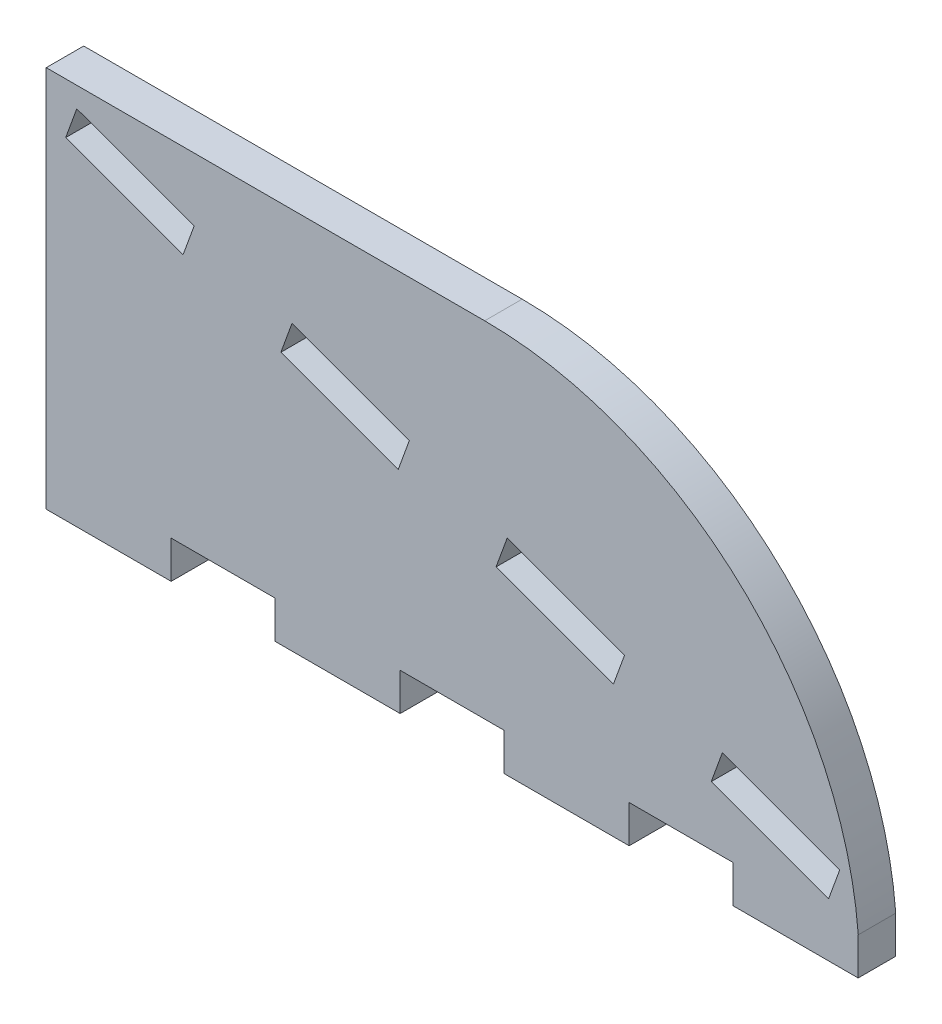
SolidWorks part; units mm, degrees
ref_plane "Front Plane" through (0, 0, 0) normal (0, 0, 1) x (1, 0, 0)
ref_plane "Top Plane" through (0, 0, 0) normal (0, 1, 0) x (1, 0, 0)
ref_plane "Right Plane" through (0, 0, 0) normal (1, 0, 0) x (0, 0, -1)
sketch "Sketch1" plane through (0, 0, 0) normal (0, 0, 1) x (1, 0, 0)
  line L0 (0, 0) -> (-0.01, 0)
  line L1 (-46.67, 0) -> (-46.67, -3)
  line L2 (-46.67, 0) -> (-55, 0)
  line L3 (-65, 0) -> (-65, -3)
  line L4 (-65, -3) -> (-55, -3)
  line L5 (-55, 0) -> (-55, -3)
  line L6 (-46.67, -3) -> (-36.67, -3)
  line L7 (-36.67, 0) -> (-36.67, -3)
  line L8 (-28.34, 0) -> (-28.34, -3)
  line L9 (-28.34, -3) -> (-18.34, -3)
  line L10 (-18.34, 0) -> (-18.34, -3)
  line L11 (-10.01, 0) -> (-10.01, -3)
  line L12 (-10.01, -3) -> (-0.01, -3)
  line L13 (-0.01, 0) -> (-0.01, -3)
  line L14 (-65, 0) -> (-65, 27.6121)
  line L15 (-65, 27.6121) -> (0, 27.6121)
  line L16 (0, 27.6121) -> (0, 0)
  line L17 (-63.0003, 24.7603) -> (-1.9203, 2.529) construction
  line L18 (-63.445, 23.5387) -> (-62.5557, 25.9819)
  line L19 (-62.5557, 25.9819) -> (-53.1588, 22.5617)
  line L20 (-53.1588, 22.5617) -> (-54.048, 20.1185)
  line L21 (-63.445, 23.5387) -> (-54.048, 20.1185)
  line L22 (-45.3312, 19.7127) -> (-35.9342, 16.2925)
  line L23 (-46.2204, 17.2695) -> (-36.8235, 13.8493)
  line L24 (-35.9342, 16.2925) -> (-36.8235, 13.8493)
  line L25 (-46.2204, 17.2695) -> (-45.3312, 19.7127)
  line L26 (-28.1066, 13.4435) -> (-18.7097, 10.0233)
  line L27 (-28.9958, 11.0003) -> (-19.5989, 7.5801)
  line L28 (-18.7097, 10.0233) -> (-19.5989, 7.5801)
  line L29 (-28.9958, 11.0003) -> (-28.1066, 13.4435)
  line L30 (-10.882, 7.1743) -> (-1.4851, 3.7541)
  line L31 (-11.7713, 4.7311) -> (-2.3743, 1.3109)
  line L32 (-1.4851, 3.7541) -> (-2.3743, 1.3109)
  line L33 (-11.7713, 4.7311) -> (-10.882, 7.1743)
  line L34 (-28.34, 0) -> (-36.67, 0)
  line L35 (-10.01, 0) -> (-18.34, 0)
  point P27 (-53.6034, 21.3401)
  dimension "D1" = 65
  dimension "D2" = 10
  dimension "D3" = 3
  dimension "D5" = 65
  dimension "D6" = 10
  dimension "D7" = 1.9997
  dimension "D8" = 1.3
  dimension "D4" = 4
  dimension "D9" = 4
extrude "Boss-Extrude1" add sketch "Sketch1" along normal blind 3
fillet "Fillet1" radius 30 1 edges at (0, 27.6121, 1.5)
